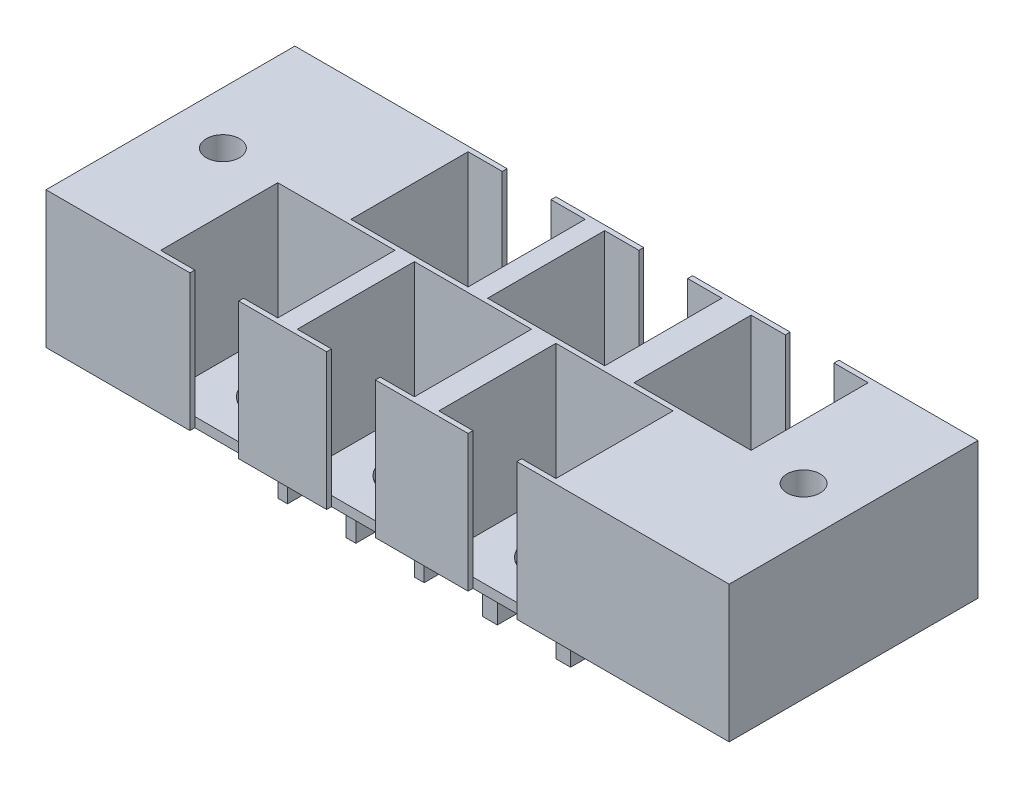
SolidWorks part; units mm, degrees
ref_plane "Front Plane" through (0, 0, 0) normal (0, 0, 1) x (1, 0, 0)
ref_plane "Top Plane" through (0, 0, 0) normal (0, 1, 0) x (1, 0, 0)
ref_plane "Right Plane" through (0, 0, 0) normal (1, 0, 0) x (0, 0, -1)
sketch "Sketch1" plane through (0, 0, 0) normal (0, 1, 0) x (1, 0, 0)
  line L0 (-18.2354, 7.7993) -> (-18.2354, -4.2007)
  line L2 (-6.2354, -4.2007) -> (-6.2354, 7.7993)
  line L3 (-6.2354, 7.7993) -> (-18.2354, 7.7993)
  line L4 (-18.2354, -4.2007) -> (-6.2354, -4.2007)
  line L5 (-18.2354, 7.7993) -> (-6.2354, -4.2007) construction
  line L6 (-18.2354, -4.2007) -> (-6.2354, 7.7993) construction
  line L7 (-12.2354, 7.7993) -> (-12.2354, -4.2007) construction
  line L8 (-5.7354, 8.2993) -> (-18.7354, 8.2993)
  line L9 (-18.7354, 8.2993) -> (-18.7354, -4.7007)
  line L11 (-5.7354, -4.7007) -> (-5.7354, 8.2993)
  line L12 (-18.7354, -4.7007) -> (-5.7354, -4.7007) construction
  line L13 (-18.7354, -4.7007) -> (-14.7354, -4.7007)
  line L14 (-5.7354, -4.7007) -> (-9.7354, -4.7007)
  line L15 (-14.7354, -4.7007) -> (-14.7354, -4.2007)
  line L16 (-9.7354, -4.7007) -> (-9.7354, -4.2007)
  line L17 (-5.7354, -4.7007) -> (-4.7354, -4.7007)
  line L21 (8.2646, -4.7007) -> (9.7646, -4.7007)
  line L22 (2.2646, 20.7993) -> (1.2646, 20.7993)
  line L23 (15.2646, 20.7993) -> (17.2646, 20.7993)
  line L24 (22.7646, -4.7007) -> (40.5146, -4.7007)
  line L25 (30.2646, 20.7993) -> (40.5146, 20.7993)
  line L26 (40.5146, 20.7993) -> (40.5146, -4.7007)
  line L27 (-18.7354, -4.7007) -> (-29.4854, -4.7007)
  line L28 (-29.4854, -4.7007) -> (-29.4854, 20.7993)
  line L29 (-29.4854, 20.7993) -> (-11.7354, 20.7993)
  line L30 (-29.4854, 8.0493) -> (40.5146, 8.0493) construction
  line L31 (-24.1104, -4.7007) -> (-24.1104, 20.7993) construction
  line L32 (35.3896, 20.7993) -> (35.3896, -4.7007) construction
  line L33 (-8.7354, -4.7007) -> (-8.7354, 20.2993) construction
  line L34 (-11.2354, 14.2993) -> (29.7646, 14.2993) construction
  line L35 (-18.2354, 1.7993) -> (20.0146, 1.7993) construction
  line L36 (20.0146, 20.7993) -> (20.0146, -4.7007) construction
  line L37 (-18.2354, -1.2007) -> (22.2646, -1.2007) construction
  line L38 (19.2646, 20.7993) -> (20.7646, 20.7993)
  line L40 (19.2646, -4.7007) -> (20.7646, -4.7007)
  line L42 (20.0146, -4.7007) -> (20.0146, 20.7993) construction
  line L43 (19.2646, 8.0493) -> (20.7646, 8.0493) construction
  line L44 (-9.2354, 1.7993) -> (-9.2354, -1.2007)
  line L45 (-8.2354, 14.2993) -> (-8.2354, -1.2007)
  line L46 (-9.2354, -1.2007) -> (-8.2354, -1.2007)
  line L47 (-9.2354, 1.7993) -> (-9.2354, 14.2993)
  line L48 (-9.2354, 14.2993) -> (-8.2354, 14.2993)
  line L49 (-2.2354, 14.2993) -> (-2.2354, -1.2007)
  line L50 (-2.2354, -1.2007) -> (-1.2354, -1.2007)
  line L51 (-1.2354, -1.2007) -> (-1.2354, 14.2993)
  line L52 (-1.2354, 14.2993) -> (-2.2354, 14.2993)
  line L53 (-4.2354, 1.7993) -> (7.7646, 1.7993) construction
  line L54 (-11.2354, 14.2993) -> (0.7646, 14.2993) construction
  line L55 (5.7646, 14.2993) -> (5.7646, -1.2007)
  line L56 (5.7646, -1.2007) -> (4.7646, -1.2007)
  line L57 (4.7646, -1.2007) -> (4.7646, 14.2993)
  line L58 (4.7646, 14.2993) -> (5.7646, 14.2993)
  line L59 (11.7646, 14.2993) -> (11.7646, -1.2007)
  line L60 (13.2646, 1.7993) -> (13.2646, 14.2993)
  line L61 (13.2646, 14.2993) -> (11.7646, 14.2993)
  line L62 (11.7646, -1.2007) -> (13.2646, -1.2007)
  line L63 (13.2646, -1.2007) -> (13.2646, 1.7993)
  line L64 (20.7646, 14.2993) -> (20.7646, -1.2007)
  line L65 (20.7646, -1.2007) -> (19.2646, -1.2007)
  line L66 (19.2646, -1.2007) -> (19.2646, 14.2993)
  line L67 (19.2646, 14.2993) -> (20.7646, 14.2993)
  circle A0 centre (-12.2354, 1.7993) radius 3
  circle A2 centre (35.3896, 8.0493) radius 1.7
  circle A3 centre (-24.1104, 8.0493) radius 1.7
  point P48 (20.0146, 8.0493)
  line B0 (0.7646, 8.2993) -> (0.7646, 20.2993)
  line B1 (-11.2354, 20.2993) -> (-11.2354, 8.2993)
  line B2 (-11.2354, 8.2993) -> (0.7646, 8.2993)
  line B3 (0.7646, 20.2993) -> (-11.2354, 20.2993)
  line B4 (0.7646, 8.2993) -> (-11.2354, 20.2993) construction
  line B5 (0.7646, 20.2993) -> (-11.2354, 8.2993) construction
  line B6 (-5.2354, 8.2993) -> (-5.2354, 20.2993) construction
  line B7 (-11.7354, 7.7993) -> (1.2646, 7.7993)
  line B8 (1.2646, 7.7993) -> (1.2646, 20.7993)
  line B9 (-11.7354, 20.7993) -> (-11.7354, 7.7993)
  line B10 (1.2646, 20.7993) -> (-2.7354, 20.7993)
  line B11 (-11.7354, 20.7993) -> (-7.7354, 20.7993)
  line B12 (-2.7354, 20.7993) -> (-2.7354, 20.2993)
  line B13 (-7.7354, 20.7993) -> (-7.7354, 20.2993)
  circle B14 centre (-5.2354, 14.2993) radius 3
  line B15 (-4.2354, 7.7993) -> (-4.2354, -4.2007)
  line B16 (7.7646, -4.2007) -> (7.7646, 7.7993)
  line B17 (7.7646, 7.7993) -> (-4.2354, 7.7993)
  line B18 (-4.2354, -4.2007) -> (7.7646, -4.2007)
  line B19 (-4.2354, 7.7993) -> (7.7646, -4.2007) construction
  line B20 (-4.2354, -4.2007) -> (7.7646, 7.7993) construction
  line B21 (1.7646, 7.7993) -> (1.7646, -4.2007) construction
  line B22 (8.2646, 8.2993) -> (-4.7354, 8.2993)
  line B23 (-4.7354, 8.2993) -> (-4.7354, -4.7007)
  line B24 (8.2646, -4.7007) -> (8.2646, 8.2993)
  line B25 (-4.7354, -4.7007) -> (-0.7354, -4.7007)
  line B26 (8.2646, -4.7007) -> (4.2646, -4.7007)
  line B27 (-0.7354, -4.7007) -> (-0.7354, -4.2007)
  line B28 (4.2646, -4.7007) -> (4.2646, -4.2007)
  circle B29 centre (1.7646, 1.7993) radius 3
  line B30 (14.7646, 8.2993) -> (14.7646, 20.2993)
  line B31 (2.7646, 20.2993) -> (2.7646, 8.2993)
  line B32 (2.7646, 8.2993) -> (14.7646, 8.2993)
  line B33 (14.7646, 20.2993) -> (2.7646, 20.2993)
  line B34 (14.7646, 8.2993) -> (2.7646, 20.2993) construction
  line B35 (14.7646, 20.2993) -> (2.7646, 8.2993) construction
  line B36 (8.7646, 8.2993) -> (8.7646, 20.2993) construction
  line B37 (2.2646, 7.7993) -> (15.2646, 7.7993)
  line B38 (15.2646, 7.7993) -> (15.2646, 20.7993)
  line B39 (2.2646, 20.7993) -> (2.2646, 7.7993)
  line B40 (15.2646, 20.7993) -> (11.2646, 20.7993)
  line B41 (2.2646, 20.7993) -> (6.2646, 20.7993)
  line B42 (11.2646, 20.7993) -> (11.2646, 20.2993)
  line B43 (6.2646, 20.7993) -> (6.2646, 20.2993)
  circle B44 centre (8.7646, 14.2993) radius 3
  line B45 (10.2646, 7.7993) -> (10.2646, -4.2007)
  line B46 (22.2646, -4.2007) -> (22.2646, 7.7993)
  line B47 (22.2646, 7.7993) -> (10.2646, 7.7993)
  line B48 (10.2646, -4.2007) -> (22.2646, -4.2007)
  line B49 (10.2646, 7.7993) -> (22.2646, -4.2007) construction
  line B50 (10.2646, -4.2007) -> (22.2646, 7.7993) construction
  line B51 (16.2646, 7.7993) -> (16.2646, -4.2007) construction
  line B52 (22.7646, 8.2993) -> (9.7646, 8.2993)
  line B53 (9.7646, 8.2993) -> (9.7646, -4.7007)
  line B54 (22.7646, -4.7007) -> (22.7646, 8.2993)
  line B55 (9.7646, -4.7007) -> (13.7646, -4.7007)
  line B56 (22.7646, -4.7007) -> (18.7646, -4.7007)
  line B57 (13.7646, -4.7007) -> (13.7646, -4.2007)
  line B58 (18.7646, -4.7007) -> (18.7646, -4.2007)
  circle B59 centre (16.2646, 1.7993) radius 3
  line B60 (29.7646, 8.2993) -> (29.7646, 20.2993)
  line B61 (17.7646, 20.2993) -> (17.7646, 8.2993)
  line B62 (17.7646, 8.2993) -> (29.7646, 8.2993)
  line B63 (29.7646, 20.2993) -> (17.7646, 20.2993)
  line B64 (29.7646, 8.2993) -> (17.7646, 20.2993) construction
  line B65 (29.7646, 20.2993) -> (17.7646, 8.2993) construction
  line B66 (23.7646, 8.2993) -> (23.7646, 20.2993) construction
  line B67 (17.2646, 7.7993) -> (30.2646, 7.7993)
  line B68 (30.2646, 7.7993) -> (30.2646, 20.7993)
  line B69 (17.2646, 20.7993) -> (17.2646, 7.7993)
  line B70 (30.2646, 20.7993) -> (26.2646, 20.7993)
  line B71 (17.2646, 20.7993) -> (21.2646, 20.7993)
  line B72 (26.2646, 20.7993) -> (26.2646, 20.2993)
  line B73 (21.2646, 20.7993) -> (21.2646, 20.2993)
  circle B74 centre (23.7646, 14.2993) radius 3
  dimension "D1" = 12
  dimension "D2" = 12
  dimension "D4" = 4
  dimension "D5" = 4
  dimension "D6" = 0
  dimension "D7" = 7
  dimension "D8" = 7
  dimension "D9" = 14
  dimension "D10" = 0
  dimension "D11" = 0
  dimension "D12" = 7
  dimension "D13" = 0
  dimension "D14" = 7.5
  dimension "D15" = 0
  dimension "D16" = 7.5
  dimension "D17" = 36
  dimension "D18" = 49
  dimension "D19" = 70
  dimension "D20" = 17.75
  dimension "D21" = 17.75
  dimension "D22" = 59.5
  dimension "D23" = 3.5
  dimension "D26" = 3.75
  dimension "D28" = 6.5
  dimension "D29" = 19
  dimension "D30" = 25.5
  dimension "D31" = 12.5
  dimension "D24" = 3
  dimension "D3" = 0.5
sketch_block_instance "Block1-1"
sketch_block "Block1"
sketch_block_instance "Block1-2"
sketch_block_instance "Block1-3"
sketch_block_instance "Block1-4"
sketch_block_instance "Block1-5" parameters "D3"=2.8156, "D23"=1.8606, "D1"=33.2541, "D2"=11.7273, "D4"=4.788, "D5"=4.1186, "D6"=0.0715, "D7"=12, "D8"=12, "D9"=12, "D10"=0.0459, "D11"=1.0511, "D12"=27.274, "D13"=1.7403, "D14"=11.648, "D15"=0.7916, "D16"=16.8895, "D17"=12, "D18"=13, "D19"=25.5, "D20"=17.6965, "D21"=17.8035, "D22"=25.5, "D24"=25, "D25"=25.5, "D26"=8.7706, "D27"=25.5, "D28"=12, "D29"=12, "D30"=17.75, "D31"=12, "D32"=25.5
extrude "Boss-Extrude1" add sketch "Sketch1" along normal blind 1 contours B59 L66 B47 B37 L60 | B37 L59 L62 L63 L60 | B59 L63 L62 L59 B37 B45 B48 B46 B47 L64 L65 L66 | L64 B47 L66 L65 | L67 B74 L64 B52 B62 B60 B63 B61 L66 | B52 L64 L67 L66 | B44 L55 B22 B32 L59 | L59 B32 L60 L61 | B44 L61 L60 B32 B30 B33 B31 B22 L57 L58 | B22 L55 L58 L57 | B29 L51 L50 L49 B7 B15 B18 B16 B17 L55 L56 L57 | L55 B17 L57 L56 | B7 L49 L50 L51 | B29 L57 B17 B7 L51 | B14 L45 L8 B2 L49 | L49 B2 L51 L52 | B14 L52 L51 B2 B0 B3 B1 L8 L47 L48 | L48 L47 L8 L45 | L44 A0 L47 L3 L0 L4 L2 L45 L46 | L47 L44 L46 L45 L3 | B9 L29 L28 L27 L9 L8 A3 | B13 B11 B9 L8 B1 B3 | B9 L8 L9 L13 L15 L4 L0 L3 | L8 B9 L3 L47 | L47 L3 L45 L8 | L3 B7 L11 L8 L45 | B7 L2 L4 L16 L14 L11 | B23 B7 L11 L17 | B23 B2 L11 B7 | B2 B23 B7 L49 | B25 B27 B18 B15 B7 B23 | B8 B22 B2 L51 B7 | L49 B7 L51 B2 | B39 L22 B8 B22 | B43 B41 B39 B22 B31 B33 | B39 B22 B8 B17 | B22 B39 B17 L57 | B22 B8 B10 B12 B3 B0 | B17 B37 B24 B22 L55 | L55 B22 L57 B17 | B53 B37 B24 L21 | B37 B16 B18 B28 B26 B24 | B53 B32 B24 B37 | B32 B53 B37 L59 | B55 B57 B48 B45 B37 B53 | L59 B37 L60 B32 | B38 B52 B32 L60 B37 | B52 B38 B40 B42 B33 B30 | B73 B71 L38 B69 B52 B61 B63 | B69 L23 B38 B52 | B69 B52 B38 B47 | B52 B69 B47 L66 | L64 B52 L66 B47 | B68 B67 B54 L24 L26 L25 A2 | B70 B72 B63 B60 B62 B54 B67 B68 | B67 B46 B48 B58 B56 L40 B54 | B47 B67 B54 B52 L64 region at (-14.9854, 0, -7.6296) region at (-18.3831, 0, -1.7993) region at (-10.4854, 0, -8.0493) region at (-8.7354, 0, -8.0493) region at (-8.7354, 0, -3.2993) region at (-11.6042, 0, -14.5493) region at (-21.9077, 0, -9.6626) region at (-7.9854, 0, 4.332) region at (-6.9854, 0, -8.0493) region at (-8.7354, 0, -11.2993) region at (-10.2354, 0, -8.469) region at (-5.2354, 0, -10.1827) region at (-5.2354, 0, -1.5493) region at (-5.2354, 0, -8.0493) region at (-4.6042, 0, -1.5493) region at (-3.4854, 0, -8.0493) region at (-1.7354, 0, -11.2993) region at (-2.6042, 0, -20.5493) region at (-3.2354, 0, -7.6296) region at (-1.7354, 0, -8.0493) region at (-1.7354, 0, -3.2993) region at (0.0146, 0, -8.0493) region at (1.7646, 0, -14.5493) region at (6.0146, 0, 4.332) region at (1.7646, 0, -5.9159) region at (1.7646, 0, -8.0493) region at (4.2646, 0, -20.668) region at (3.5146, 0, -8.0493) region at (7.0146, 0, -8.0493) region at (9.0146, 0, -1.5493) region at (5.2646, 0, -3.2993) region at (2.9343, 0, -14.2993) region at (5.2646, 0, -8.0493) region at (9.0146, 0, -8.0493) region at (9.8958, 0, -1.5493) region at (5.2646, 0, -11.2993) region at (11.3958, 0, -20.5493) region at (8.7646, 0, -10.1827) region at (10.7646, 0, -8.0493) region at (11.0146, 0, -7.6296) region at (14.2646, 0, -8.0493) region at (16.2646, 0, -14.5493) region at (12.5146, 0, -11.2993) region at (12.5146, 0, -8.0493) region at (12.5146, 0, -3.2993) region at (20.5146, 0, 4.332) region at (16.2646, 0, -8.0493) region at (18.2646, 0, -20.668) region at (16.2646, 0, -5.9159) region at (18.2646, 0, -8.0493) region at (21.7646, 0, -8.0493) region at (17.9343, 0, -14.2993) region at (20.0146, 0, -3.2993) region at (20.0146, 0, -8.0493) region at (32.9852, 0, -6.2883) region at (22.9147, 0, -8.0493) region at (20.0146, 0, -11.2993)
extrude "Boss-Extrude2" add sketch "Sketch1<4>" along normal blind 14 contours B9 L8 L9 L13 L15 L4 L0 L3 | B13 B11 B9 L8 B1 B3 | L8 B9 L3 L47 | B7 L2 L4 L16 L14 L11 | L47 L3 L45 L8 | L3 B7 L11 L8 L45 | B23 B2 L11 B7 | B23 B7 L11 L17 | B25 B27 B18 B15 B7 B23 | B2 B23 B7 L49 | L49 B7 L51 B2 | B8 B22 B2 L51 B7 | B22 B8 B10 B12 B3 B0 | B39 L22 B8 B22 | B39 B22 B8 B17 | B43 B41 B39 B22 B31 B33 | B22 B39 B17 L57 | L55 B22 L57 B17 | B17 B37 B24 B22 L55 | B37 B16 B18 B28 B26 B24 | B53 B32 B24 B37 | B32 B53 B37 L59 | B53 B37 B24 L21 | B55 B57 B48 B45 B37 B53 | L59 B37 L60 B32 | B38 B52 B32 L60 B37 | B52 B38 B40 B42 B33 B30 | B69 B52 B38 B47 | B52 B69 B47 L66 | B73 B71 L38 B69 B52 B61 B63 | L64 B52 L66 B47 | B47 B67 B54 B52 L64 | B67 B46 B48 B58 B56 L40 B54 | B70 B72 B63 B60 B62 B54 B67 B68 | B68 B67 B54 L24 L26 L25 A2 | B9 L29 L28 L27 L9 L8 A3 | B69 L23 B38 B52 region at (-18.3831, 0, -1.7993) region at (-10.4854, 0, -8.0493) region at (-8.7354, 0, -8.0493) region at (-11.6042, 0, -14.5493) region at (-21.9077, 0, -9.6626) region at (-7.9854, 0, 4.332) region at (-6.9854, 0, -8.0493) region at (-5.2354, 0, -1.5493) region at (-5.2354, 0, -8.0493) region at (-4.6042, 0, -1.5493) region at (-3.4854, 0, -8.0493) region at (-2.6042, 0, -20.5493) region at (-1.7354, 0, -8.0493) region at (0.0146, 0, -8.0493) region at (1.7646, 0, -14.5493) region at (6.0146, 0, 4.332) region at (1.7646, 0, -8.0493) region at (4.2646, 0, -20.668) region at (3.5146, 0, -8.0493) region at (7.0146, 0, -8.0493) region at (9.0146, 0, -1.5493) region at (5.2646, 0, -8.0493) region at (9.0146, 0, -8.0493) region at (9.8958, 0, -1.5493) region at (11.3958, 0, -20.5493) region at (10.7646, 0, -8.0493) region at (14.2646, 0, -8.0493) region at (16.2646, 0, -14.5493) region at (12.5146, 0, -8.0493) region at (20.5146, 0, 4.332) region at (16.2646, 0, -8.0493) region at (18.2646, 0, -20.668) region at (18.2646, 0, -8.0493) region at (21.7646, 0, -8.0493) region at (20.0146, 0, -8.0493) region at (32.9852, 0, -6.2883) region at (22.9147, 0, -8.0493)
sketch "Sketch1<4>" plane through (0, 0, 0) normal (0, 1, 0) x (1, 0, 0) same geometry as "Sketch1"
extrude "Boss-Extrude3" add sketch "Sketch1<5>" against normal blind 5 contours L48 L47 L8 L45 | L47 L44 L46 L45 L3 | L47 L3 L45 L8 | B7 L49 L50 L51 | L49 B2 L51 L52 | L49 B7 L51 B2 | L55 B17 L57 L56 | B22 L55 L58 L57 | L55 B22 L57 B17 | L59 B32 L60 L61 | L59 B37 L60 B32 | B37 L59 L62 L63 L60 | L64 B47 L66 L65 | L64 B52 L66 B47 | B52 L64 L67 L66 region at (-8.7354, 0, -8.0493) region at (-8.7354, 0, -3.2993) region at (-8.7354, 0, -11.2993) region at (-1.7354, 0, -11.2993) region at (-1.7354, 0, -8.0493) region at (-1.7354, 0, -3.2993) region at (5.2646, 0, -3.2993) region at (5.2646, 0, -8.0493) region at (5.2646, 0, -11.2993) region at (12.5146, 0, -11.2993) region at (12.5146, 0, -8.0493) region at (12.5146, 0, -3.2993) region at (20.0146, 0, -3.2993) region at (20.0146, 0, -8.0493) region at (20.0146, 0, -11.2993)
sketch "Sketch1<5>" plane through (0, 0, 0) normal (0, 1, 0) x (1, 0, 0) same geometry as "Sketch1"
